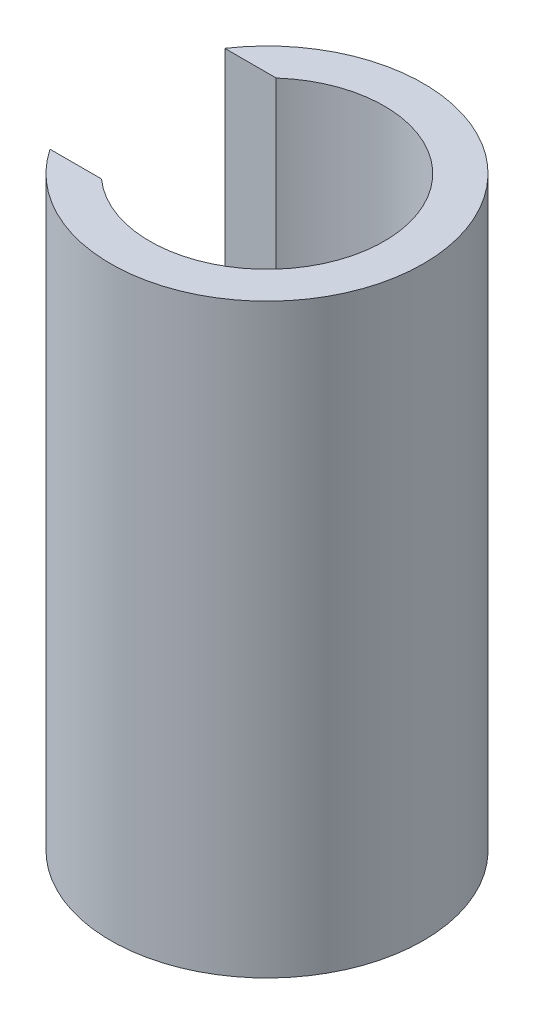
SolidWorks part; units mm, degrees
ref_plane "前基準面" through (0, 0, 0) normal (0, 0, 1) x (1, 0, 0)
ref_plane "上基準面" through (0, 0, 0) normal (0, 1, 0) x (1, 0, 0)
ref_plane "右基準面" through (0, 0, 0) normal (1, 0, 0) x (0, 0, -1)
ref_axis "基準軸1" through (0, -55, 0) along (0, 1, 0)
ref_axis "基準軸2" through (-88.99, 0, 0) along (1, 0, 0)
ref_axis "基準軸3" through (0, 0, 55) along (0, 0, -1)
sketch "草圖1" plane through (0, 0, 0) normal (0, 1, 0) x (1, 0, 0)
  circle A0 centre (0, 0) radius 3
  circle A1 centre (0, 0) radius 4
  dimension "D1" = 6
  dimension "D2" = 8
extrude "填料-伸長1" add sketch "草圖1" along normal blind 15
sketch "草圖2" plane through (0, 15, 0) normal (0, 1, 0) x (1, 0, 0)
  line L1 (-4, -2.2361) -> (-2, -2.2361)
  line L2 (-4, -2.2361) -> (-4, 2.2361)
  line L3 (-4, 2.2361) -> (-2, 2.2361)
  line L4 (-2, -2.2361) -> (-2, 2.2361)
  line L5 (-55, 0) -> (55, 0) construction
  circle A0 centre (0, 0) radius 4 construction
  circle A1 centre (0, 0) radius 3 construction
  point P4 (-2, 0)
  dimension "D1" = 2
extrude "除料-伸長1" cut sketch "草圖2" against normal blind 15
